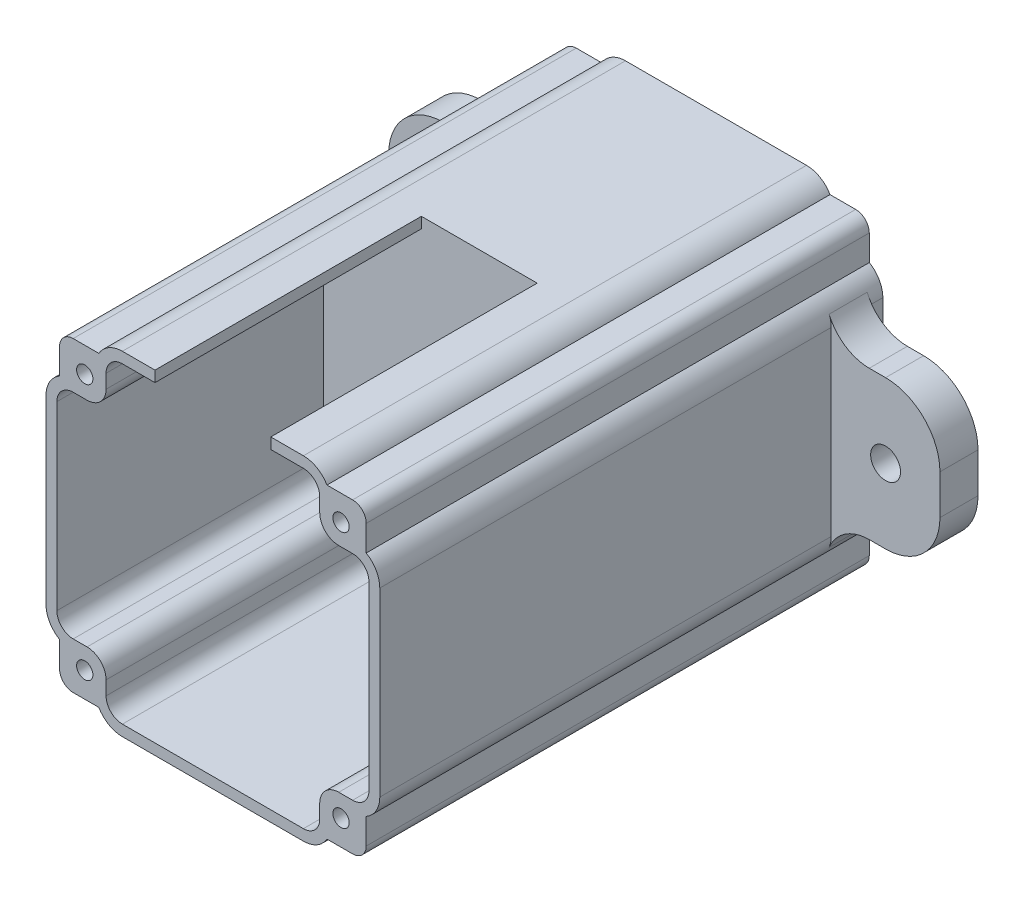
SolidWorks part; units mm, degrees
ref_plane "Front Plane" through (0, 0, 0) normal (0, 0, 1) x (1, 0, 0)
ref_plane "Top Plane" through (0, 0, 0) normal (0, 1, 0) x (1, 0, 0)
ref_plane "Right Plane" through (0, 0, 0) normal (1, 0, 0) x (0, 0, -1)
sketch "Sketch1" plane through (0, 0, -54) normal (0, 0, -1) x (-1, 0, 0)
  line L0 (-25.7, -19.65) -> (-23.15, -19.65)
  line L1 (-19.65, -23.15) -> (-19.65, -25.7)
  line L2 (-16.65, -28.7) -> (16.65, -28.7)
  line L3 (19.65, -25.7) -> (19.65, -23.15)
  line L4 (23.15, -19.65) -> (25.7, -19.65)
  line L5 (28.7, -16.65) -> (28.7, 16.65)
  line L6 (25.7, 19.65) -> (23.15, 19.65)
  line L7 (19.65, 23.15) -> (19.65, 25.7)
  line L8 (16.65, 28.7) -> (10.65, 28.7)
  line L9 (-19.65, 25.7) -> (-19.65, 23.15)
  line L10 (-23.15, 19.65) -> (-25.7, 19.65)
  line L11 (-28.7, 16.65) -> (-28.7, -16.65)
  line L12 (-25.7, -18.65) -> (-23.15, -18.65)
  line L13 (-18.65, -23.15) -> (-18.65, -25.7)
  line L14 (-16.65, -27.7) -> (16.65, -27.7)
  line L15 (18.65, -25.7) -> (18.65, -23.15)
  line L16 (23.15, -18.65) -> (25.7, -18.65)
  line L17 (27.7, -16.65) -> (27.7, 16.65)
  line L18 (25.7, 18.65) -> (23.15, 18.65)
  line L19 (18.65, 23.15) -> (18.65, 25.7)
  line L20 (16.65, 27.7) -> (-16.65, 27.7)
  line L21 (-18.65, 25.7) -> (-18.65, 23.15)
  line L22 (-23.15, 18.65) -> (-25.7, 18.65)
  line L23 (-27.7, 16.65) -> (-27.7, -16.65)
  line L24 (-25.7, -18.65) -> (-23.15, -18.65) construction
  line L25 (-18.65, -23.15) -> (-18.65, -25.7) construction
  line L26 (-16.65, -27.7) -> (16.65, -27.7) construction
  line L27 (18.65, -25.7) -> (18.65, -23.15) construction
  line L28 (23.15, -18.65) -> (25.7, -18.65) construction
  line L29 (27.7, -16.65) -> (27.7, 16.65) construction
  line L30 (25.7, 18.65) -> (23.15, 18.65) construction
  line L31 (18.65, 23.15) -> (18.65, 25.7) construction
  line L32 (16.65, 27.7) -> (-16.65, 27.7) construction
  line L33 (-18.65, 25.7) -> (-18.65, 23.15) construction
  line L34 (-23.15, 18.65) -> (-25.7, 18.65) construction
  line L35 (-27.7, 16.65) -> (-27.7, -16.65) construction
  line L36 (-25.7, -21.65) -> (-23.15, -21.65)
  line L37 (-21.65, -23.15) -> (-21.65, -25.7)
  line L38 (-16.65, -30.7) -> (16.65, -30.7)
  line L39 (21.65, -25.7) -> (21.65, -23.15)
  line L40 (23.15, -21.65) -> (25.7, -21.65)
  line L41 (30.7, -16.65) -> (30.7, 16.65)
  line L42 (25.7, 21.65) -> (23.15, 21.65)
  line L43 (21.65, 23.15) -> (21.65, 25.7)
  line L44 (16.65, 30.7) -> (10.65, 30.7)
  line L45 (-21.65, 25.7) -> (-21.65, 23.15)
  line L46 (-23.15, 21.65) -> (-25.7, 21.65)
  line L47 (-30.7, 16.65) -> (-30.7, -16.65)
  line L48 (-10.65, 30.7) -> (-10.65, 28.7)
  line L49 (10.65, 30.7) -> (10.65, 28.7)
  line L50 (-10.65, 30.7) -> (-16.65, 30.7)
  line L51 (16.65, 30.7) -> (-16.65, 30.7) construction
  line L52 (-10.65, 28.7) -> (-16.65, 28.7)
  line L53 (16.65, 28.7) -> (-16.65, 28.7) construction
  arc A0 (-19.65, -23.15) -> (-23.15, -19.65) centre (-23.15, -23.15) ccw
  arc A1 (-19.65, -25.7) -> (-16.65, -28.7) centre (-16.65, -25.7) ccw
  arc A2 (16.65, -28.7) -> (19.65, -25.7) centre (16.65, -25.7) ccw
  arc A3 (23.15, -19.65) -> (19.65, -23.15) centre (23.15, -23.15) ccw
  arc A4 (25.7, -19.65) -> (28.7, -16.65) centre (25.7, -16.65) ccw
  arc A5 (28.7, 16.65) -> (25.7, 19.65) centre (25.7, 16.65) ccw
  arc A6 (19.65, 23.15) -> (23.15, 19.65) centre (23.15, 23.15) ccw
  arc A7 (19.65, 25.7) -> (16.65, 28.7) centre (16.65, 25.7) ccw
  arc A8 (-16.65, 28.7) -> (-19.65, 25.7) centre (-16.65, 25.7) ccw
  arc A9 (-23.15, 19.65) -> (-19.65, 23.15) centre (-23.15, 23.15) ccw
  arc A10 (-25.7, 19.65) -> (-28.7, 16.65) centre (-25.7, 16.65) ccw
  arc A11 (-28.7, -16.65) -> (-25.7, -19.65) centre (-25.7, -16.65) ccw
  arc A12 (-27.7, -16.65) -> (-25.7, -18.65) centre (-25.7, -16.65) ccw
  arc A13 (-18.65, -23.15) -> (-23.15, -18.65) centre (-23.15, -23.15) ccw
  arc A14 (-18.65, -25.7) -> (-16.65, -27.7) centre (-16.65, -25.7) ccw
  arc A15 (16.65, -27.7) -> (18.65, -25.7) centre (16.65, -25.7) ccw
  arc A16 (23.15, -18.65) -> (18.65, -23.15) centre (23.15, -23.15) ccw
  arc A17 (25.7, -18.65) -> (27.7, -16.65) centre (25.7, -16.65) ccw
  arc A18 (27.7, 16.65) -> (25.7, 18.65) centre (25.7, 16.65) ccw
  arc A19 (18.65, 23.15) -> (23.15, 18.65) centre (23.15, 23.15) ccw
  arc A20 (18.65, 25.7) -> (16.65, 27.7) centre (16.65, 25.7) ccw
  arc A21 (-16.65, 27.7) -> (-18.65, 25.7) centre (-16.65, 25.7) ccw
  arc A22 (-23.15, 18.65) -> (-18.65, 23.15) centre (-23.15, 23.15) ccw
  arc A23 (-25.7, 18.65) -> (-27.7, 16.65) centre (-25.7, 16.65) ccw
  arc A24 (-27.7, -16.65) -> (-25.7, -18.65) centre (-25.7, -16.65) ccw construction
  arc A25 (-18.65, -23.15) -> (-23.15, -18.65) centre (-23.15, -23.15) ccw construction
  arc A26 (-18.65, -25.7) -> (-16.65, -27.7) centre (-16.65, -25.7) ccw construction
  arc A27 (16.65, -27.7) -> (18.65, -25.7) centre (16.65, -25.7) ccw construction
  arc A28 (23.15, -18.65) -> (18.65, -23.15) centre (23.15, -23.15) ccw construction
  arc A29 (25.7, -18.65) -> (27.7, -16.65) centre (25.7, -16.65) ccw construction
  arc A30 (27.7, 16.65) -> (25.7, 18.65) centre (25.7, 16.65) ccw construction
  arc A31 (18.65, 23.15) -> (23.15, 18.65) centre (23.15, 23.15) ccw construction
  arc A32 (18.65, 25.7) -> (16.65, 27.7) centre (16.65, 25.7) ccw construction
  arc A33 (-16.65, 27.7) -> (-18.65, 25.7) centre (-16.65, 25.7) ccw construction
  arc A34 (-23.15, 18.65) -> (-18.65, 23.15) centre (-23.15, 23.15) ccw construction
  arc A35 (-25.7, 18.65) -> (-27.7, 16.65) centre (-25.7, 16.65) ccw construction
  arc A36 (-21.65, -23.15) -> (-23.15, -21.65) centre (-23.15, -23.15) ccw
  arc A37 (-21.65, -25.7) -> (-16.65, -30.7) centre (-16.65, -25.7) ccw
  arc A38 (16.65, -30.7) -> (21.65, -25.7) centre (16.65, -25.7) ccw
  arc A39 (23.15, -21.65) -> (21.65, -23.15) centre (23.15, -23.15) ccw
  arc A40 (25.7, -21.65) -> (30.7, -16.65) centre (25.7, -16.65) ccw
  arc A41 (30.7, 16.65) -> (25.7, 21.65) centre (25.7, 16.65) ccw
  arc A42 (21.65, 23.15) -> (23.15, 21.65) centre (23.15, 23.15) ccw
  arc A43 (21.65, 25.7) -> (16.65, 30.7) centre (16.65, 25.7) ccw
  arc A44 (-16.65, 30.7) -> (-21.65, 25.7) centre (-16.65, 25.7) ccw
  arc A45 (-23.15, 21.65) -> (-21.65, 23.15) centre (-23.15, 23.15) ccw
  arc A46 (-25.7, 21.65) -> (-30.7, 16.65) centre (-25.7, 16.65) ccw
  arc A47 (-30.7, -16.65) -> (-25.7, -21.65) centre (-25.7, -16.65) ccw
  dimension "D4" = 6
  dimension "D5" = 6
  dimension "D1" = 0
  dimension "D2" = 1
  dimension "D3" = 2
extrude "Boss-Extrude1" add sketch "Sketch1" against normal up to surface (49 mm away)
sketch "Sketch2" plane through (0, 0, -54) normal (0, 0, -1) x (-1, 0, 0)
  line L0 (-10.65, 30.7) -> (10.65, 30.7)
  line L12 (-25.7, -21.65) -> (-23.15, -21.65)
  line L13 (-21.65, -23.15) -> (-21.65, -25.7)
  line L14 (-16.65, -30.7) -> (16.65, -30.7)
  line L15 (21.65, -25.7) -> (21.65, -23.15)
  line L16 (23.15, -21.65) -> (25.7, -21.65)
  line L17 (30.7, -16.65) -> (30.7, 16.65)
  line L18 (25.7, 21.65) -> (23.15, 21.65)
  line L19 (21.65, 23.15) -> (21.65, 25.7)
  line L20 (16.65, 30.7) -> (10.65, 30.7)
  line L21 (-21.65, 25.7) -> (-21.65, 23.15)
  line L22 (-23.15, 21.65) -> (-25.7, 21.65)
  line L23 (-30.7, 16.65) -> (-30.7, -16.65)
  line L24 (-25.7, -21.65) -> (-23.15, -21.65)
  line L25 (-21.65, -23.15) -> (-21.65, -25.7)
  line L26 (-16.65, -30.7) -> (16.65, -30.7)
  line L27 (21.65, -25.7) -> (21.65, -23.15)
  line L28 (23.15, -21.65) -> (25.7, -21.65)
  line L29 (30.7, -16.65) -> (30.7, 16.65)
  line L30 (25.7, 21.65) -> (23.15, 21.65)
  line L31 (21.65, 23.15) -> (21.65, 25.7)
  line L32 (16.65, 30.7) -> (10.65, 30.7)
  line L33 (-21.65, 25.7) -> (-21.65, 23.15)
  line L34 (-23.15, 21.65) -> (-25.7, 21.65)
  line L35 (-30.7, 16.65) -> (-30.7, -16.65)
  line L52 (-28.7, -16.65) -> (-28.7, 16.65)
  line L54 (-25.7, 19.65) -> (-23.15, 19.65)
  line L56 (-19.65, 23.15) -> (-19.65, 25.7)
  line L58 (-16.65, 28.7) -> (-10.65, 28.7)
  line L60 (-10.65, 28.7) -> (-10.65, 30.7)
  line L62 (-10.65, 30.7) -> (-16.65, 30.7)
  line L63 (-10.65, 30.7) -> (-16.65, 30.7)
  line L64 (10.65, 30.7) -> (10.65, 28.7)
  line L66 (10.65, 28.7) -> (16.65, 28.7)
  line L68 (19.65, 25.7) -> (19.65, 23.15)
  line L70 (23.15, 19.65) -> (25.7, 19.65)
  line L72 (28.7, 16.65) -> (28.7, -16.65)
  line L74 (25.7, -19.65) -> (23.15, -19.65)
  line L76 (19.65, -23.15) -> (19.65, -25.7)
  line L78 (16.65, -28.7) -> (-16.65, -28.7)
  line L80 (-19.65, -25.7) -> (-19.65, -23.15)
  line L82 (-23.15, -19.65) -> (-25.7, -19.65)
  arc A12 (-30.7, -16.65) -> (-25.7, -21.65) centre (-25.7, -16.65) ccw
  arc A13 (-21.65, -23.15) -> (-23.15, -21.65) centre (-23.15, -23.15) ccw
  arc A14 (-21.65, -25.7) -> (-16.65, -30.7) centre (-16.65, -25.7) ccw
  arc A15 (16.65, -30.7) -> (21.65, -25.7) centre (16.65, -25.7) ccw
  arc A16 (23.15, -21.65) -> (21.65, -23.15) centre (23.15, -23.15) ccw
  arc A17 (25.7, -21.65) -> (30.7, -16.65) centre (25.7, -16.65) ccw
  arc A18 (30.7, 16.65) -> (25.7, 21.65) centre (25.7, 16.65) ccw
  arc A19 (21.65, 23.15) -> (23.15, 21.65) centre (23.15, 23.15) ccw
  arc A20 (21.65, 25.7) -> (16.65, 30.7) centre (16.65, 25.7) ccw
  arc A21 (-16.65, 30.7) -> (-21.65, 25.7) centre (-16.65, 25.7) ccw
  arc A22 (-23.15, 21.65) -> (-21.65, 23.15) centre (-23.15, 23.15) ccw
  arc A23 (-25.7, 21.65) -> (-30.7, 16.65) centre (-25.7, 16.65) ccw
  arc A24 (-30.7, -16.65) -> (-25.7, -21.65) centre (-25.7, -16.65) ccw
  arc A25 (-21.65, -23.15) -> (-23.15, -21.65) centre (-23.15, -23.15) ccw
  arc A26 (-21.65, -25.7) -> (-16.65, -30.7) centre (-16.65, -25.7) ccw
  arc A27 (16.65, -30.7) -> (21.65, -25.7) centre (16.65, -25.7) ccw
  arc A28 (23.15, -21.65) -> (21.65, -23.15) centre (23.15, -23.15) ccw
  arc A29 (25.7, -21.65) -> (30.7, -16.65) centre (25.7, -16.65) ccw
  arc A30 (30.7, 16.65) -> (25.7, 21.65) centre (25.7, 16.65) ccw
  arc A31 (21.65, 23.15) -> (23.15, 21.65) centre (23.15, 23.15) ccw
  arc A32 (21.65, 25.7) -> (16.65, 30.7) centre (16.65, 25.7) ccw
  arc A33 (-16.65, 30.7) -> (-21.65, 25.7) centre (-16.65, 25.7) ccw
  arc A34 (-23.15, 21.65) -> (-21.65, 23.15) centre (-23.15, 23.15) ccw
  arc A35 (-25.7, 21.65) -> (-30.7, 16.65) centre (-25.7, 16.65) ccw
  arc A48 (-28.7, -16.65) -> (-25.7, -19.65) centre (-25.7, -16.65) ccw
  arc A50 (-25.7, 19.65) -> (-28.7, 16.65) centre (-25.7, 16.65) ccw
  arc A52 (-23.15, 19.65) -> (-19.65, 23.15) centre (-23.15, 23.15) ccw
  arc A54 (-16.65, 28.7) -> (-19.65, 25.7) centre (-16.65, 25.7) ccw
  arc A56 (19.65, 25.7) -> (16.65, 28.7) centre (16.65, 25.7) ccw
  arc A58 (19.65, 23.15) -> (23.15, 19.65) centre (23.15, 23.15) ccw
  arc A60 (28.7, 16.65) -> (25.7, 19.65) centre (25.7, 16.65) ccw
  arc A62 (25.7, -19.65) -> (28.7, -16.65) centre (25.7, -16.65) ccw
  arc A64 (23.15, -19.65) -> (19.65, -23.15) centre (23.15, -23.15) ccw
  arc A66 (16.65, -28.7) -> (19.65, -25.7) centre (16.65, -25.7) ccw
  arc A68 (-19.65, -25.7) -> (-16.65, -28.7) centre (-16.65, -25.7) ccw
  arc A70 (-19.65, -23.15) -> (-23.15, -19.65) centre (-23.15, -23.15) ccw
  dimension "D1" = 0
extrude "Boss-Extrude2" add sketch "Sketch2" along normal blind 1.5
sketch "Sketch3" plane through (0, 0, -55.5) normal (0, 0, -1) x (-1, 0, 0)
  line L5 (-21.65, 25.7) -> (-21.65, 23.15) construction
  line L6 (-23.15, 21.65) -> (-25.7, 21.65) construction
  line L7 (-28.2, 16.65) -> (-28.2, 25.7) construction
  line L13 (-25.7, 28.2) -> (-16.65, 28.2) construction
  line L14 (-21.65, 25.7) -> (-21.65, 23.15)
  line L15 (-23.15, 21.65) -> (-25.7, 21.65)
  line L21 (-28.2, 20.9801) -> (-28.2, 25.7)
  line L22 (-25.7, 28.2) -> (-20.9801, 28.2)
  line L23 (21.65, 23.15) -> (21.65, 25.7) construction
  line L92 (25.7, 21.65) -> (23.15, 21.65) construction
  line L93 (28.2, 25.7) -> (28.2, 16.65) construction
  line L94 (16.65, 28.2) -> (25.7, 28.2) construction
  line L95 (21.65, 23.15) -> (21.65, 25.7)
  line L96 (25.7, 21.65) -> (23.15, 21.65)
  line L97 (28.2, 25.7) -> (28.2, 20.9801)
  line L98 (20.9801, 28.2) -> (25.7, 28.2)
  line L99 (-25.7, -21.65) -> (-23.15, -21.65) construction
  line L100 (-21.65, -23.15) -> (-21.65, -25.7) construction
  line L101 (-16.65, -28.2) -> (-25.7, -28.2) construction
  line L102 (-28.2, -25.7) -> (-28.2, -16.65) construction
  line L103 (-25.7, -21.65) -> (-23.15, -21.65)
  line L104 (-21.65, -23.15) -> (-21.65, -25.7)
  line L105 (-20.9801, -28.2) -> (-25.7, -28.2)
  line L106 (-28.2, -25.7) -> (-28.2, -20.9801)
  line L107 (25.7, -28.2) -> (16.65, -28.2) construction
  line L108 (21.65, -25.7) -> (21.65, -23.15) construction
  line L109 (23.15, -21.65) -> (25.7, -21.65) construction
  line L110 (25.7, -28.2) -> (20.9801, -28.2)
  line L111 (21.65, -25.7) -> (21.65, -23.15)
  line L112 (23.15, -21.65) -> (25.7, -21.65)
  line L113 (28.2, -16.65) -> (28.2, -25.7) construction
  line L114 (28.2, -20.9801) -> (28.2, -25.7)
  arc A92 (-16.65, 30.7) -> (-21.65, 25.7) centre (-16.65, 25.7) ccw construction
  arc A93 (-23.15, 21.65) -> (-21.65, 23.15) centre (-23.15, 23.15) ccw construction
  arc A94 (-25.7, 21.65) -> (-30.7, 16.65) centre (-25.7, 16.65) ccw construction
  arc A95 (-25.7, 28.2) -> (-28.2, 25.7) centre (-25.7, 25.7) ccw construction
  arc A96 (-20.9801, 28.2) -> (-21.65, 25.7) centre (-16.65, 25.7) ccw
  arc A97 (-23.15, 21.65) -> (-21.65, 23.15) centre (-23.15, 23.15) ccw
  arc A98 (-25.7, 21.65) -> (-28.2, 20.9801) centre (-25.7, 16.65) ccw
  arc A99 (-25.7, 28.2) -> (-28.2, 25.7) centre (-25.7, 25.7) ccw
  arc A100 (21.65, 25.7) -> (16.65, 30.7) centre (16.65, 25.7) ccw construction
  arc A101 (21.65, 23.15) -> (23.15, 21.65) centre (23.15, 23.15) ccw construction
  arc A102 (30.7, 16.65) -> (25.7, 21.65) centre (25.7, 16.65) ccw construction
  arc A103 (28.2, 25.7) -> (25.7, 28.2) centre (25.7, 25.7) ccw construction
  arc A104 (21.65, 25.7) -> (20.9801, 28.2) centre (16.65, 25.7) ccw
  arc A105 (21.65, 23.15) -> (23.15, 21.65) centre (23.15, 23.15) ccw
  arc A106 (28.2, 20.9801) -> (25.7, 21.65) centre (25.7, 16.65) ccw
  arc A107 (28.2, 25.7) -> (25.7, 28.2) centre (25.7, 25.7) ccw
  arc A108 (-30.7, -16.65) -> (-25.7, -21.65) centre (-25.7, -16.65) ccw construction
  arc A109 (-21.65, -23.15) -> (-23.15, -21.65) centre (-23.15, -23.15) ccw construction
  arc A110 (-21.65, -25.7) -> (-16.65, -30.7) centre (-16.65, -25.7) ccw construction
  arc A111 (-28.2, -25.7) -> (-25.7, -28.2) centre (-25.7, -25.7) ccw construction
  arc A112 (-28.2, -20.9801) -> (-25.7, -21.65) centre (-25.7, -16.65) ccw
  arc A113 (-21.65, -23.15) -> (-23.15, -21.65) centre (-23.15, -23.15) ccw
  arc A114 (-21.65, -25.7) -> (-20.9801, -28.2) centre (-16.65, -25.7) ccw
  arc A115 (-28.2, -25.7) -> (-25.7, -28.2) centre (-25.7, -25.7) ccw
  arc A116 (25.7, -28.2) -> (28.2, -25.7) centre (25.7, -25.7) ccw construction
  arc A117 (16.65, -30.7) -> (21.65, -25.7) centre (16.65, -25.7) ccw construction
  arc A118 (23.15, -21.65) -> (21.65, -23.15) centre (23.15, -23.15) ccw construction
  arc A119 (25.7, -21.65) -> (30.7, -16.65) centre (25.7, -16.65) ccw construction
  arc A120 (25.7, -28.2) -> (28.2, -25.7) centre (25.7, -25.7) ccw
  arc A121 (20.9801, -28.2) -> (21.65, -25.7) centre (16.65, -25.7) ccw
  arc A122 (23.15, -21.65) -> (21.65, -23.15) centre (23.15, -23.15) ccw
  arc A123 (25.7, -21.65) -> (28.2, -20.9801) centre (25.7, -16.65) ccw
  arc M25 (-30.7, -16.65) -> (-25.7, -21.65) centre (-25.7, -16.65) ccw
  line M26 (-25.7, -21.65) -> (-23.15, -21.65)
  arc M27 (-23.15, -21.65) -> (-21.65, -23.15) centre (-23.15, -23.15) cw
  line M28 (-21.65, -23.15) -> (-21.65, -25.7)
  arc M29 (-21.65, -25.7) -> (-16.65, -30.7) centre (-16.65, -25.7) ccw
  arc M31 (16.65, -30.7) -> (21.65, -25.7) centre (16.65, -25.7) ccw
  line M32 (21.65, -25.7) -> (21.65, -23.15)
  arc M33 (21.65, -23.15) -> (23.15, -21.65) centre (23.15, -23.15) cw
  line M34 (23.15, -21.65) -> (25.7, -21.65)
  arc M35 (25.7, -21.65) -> (30.7, -16.65) centre (25.7, -16.65) ccw
  arc M37 (30.7, 16.65) -> (25.7, 21.65) centre (25.7, 16.65) ccw
  line M38 (25.7, 21.65) -> (23.15, 21.65)
  arc M39 (23.15, 21.65) -> (21.65, 23.15) centre (23.15, 23.15) cw
  line M40 (21.65, 23.15) -> (21.65, 25.7)
  arc M41 (21.65, 25.7) -> (16.65, 30.7) centre (16.65, 25.7) ccw
  arc M43 (-16.65, 30.7) -> (-21.65, 25.7) centre (-16.65, 25.7) ccw
  line M44 (-21.65, 25.7) -> (-21.65, 23.15)
  arc M45 (-21.65, 23.15) -> (-23.15, 21.65) centre (-23.15, 23.15) cw
  line M46 (-23.15, 21.65) -> (-25.7, 21.65)
  arc M47 (-25.7, 21.65) -> (-30.7, 16.65) centre (-25.7, 16.65) ccw
extrude "Boss-Extrude3" add sketch "Sketch3" against normal up to surface (50.5 mm away) contours M47 M46 M45 M44 M43 | M41 M40 M39 M38 M37 | M29 M28 M27 M26 M25 | M35 M34 M33 M32 M31 region at (24.8618, 24.8618, -55.5) region at (-24.8618, 24.8618, -55.5) region at (24.8618, -24.8618, -55.5) region at (-24.8618, -24.8618, -55.5)
sketch "Sketch4" plane through (0, 0, -5) normal (0, 0, 1) x (1, 0, 0)
  circle A0 centre (-23.57, 23.57) radius 1.5
  circle A1 centre (23.57, 23.57) radius 1.5
  circle A2 centre (-23.57, -23.57) radius 1.5
  circle A3 centre (23.57, -23.57) radius 1.5
  dimension "D1" = 3
extrude "Cut-Extrude1" cut sketch "Sketch4" against normal blind 10
sketch "Sketch5" plane through (0, 0, -55.5) normal (0, 0, -1) x (-1, 0, 0)
  line L12 (28.2, -25.7) -> (28.2, -20.9801)
  line L13 (30.7, -16.65) -> (30.7, 16.65)
  line L14 (28.2, 20.9801) -> (28.2, 25.7)
  line L15 (25.7, 28.2) -> (20.9801, 28.2)
  line L16 (16.65, 30.7) -> (-16.65, 30.7)
  line L17 (-20.9801, 28.2) -> (-25.7, 28.2)
  line L18 (-28.2, 25.7) -> (-28.2, 20.9801)
  line L19 (-30.7, 16.65) -> (-30.7, -16.65)
  line L20 (-28.2, -20.9801) -> (-28.2, -25.7)
  line L21 (-25.7, -28.2) -> (-20.9801, -28.2)
  line L22 (-16.65, -30.7) -> (16.65, -30.7)
  line L23 (20.9801, -28.2) -> (25.7, -28.2)
  line L24 (28.2, -25.7) -> (28.2, -20.9801)
  line L25 (30.7, -16.65) -> (30.7, 16.65)
  line L26 (28.2, 20.9801) -> (28.2, 25.7)
  line L27 (25.7, 28.2) -> (20.9801, 28.2)
  line L28 (16.65, 30.7) -> (-16.65, 30.7)
  line L29 (-20.9801, 28.2) -> (-25.7, 28.2)
  line L30 (-28.2, 25.7) -> (-28.2, 20.9801)
  line L31 (-30.7, 16.65) -> (-30.7, -16.65)
  line L32 (-28.2, -20.9801) -> (-28.2, -25.7)
  line L33 (-25.7, -28.2) -> (-20.9801, -28.2)
  line L34 (-16.65, -30.7) -> (16.65, -30.7)
  line L35 (20.9801, -28.2) -> (25.7, -28.2)
  arc A12 (28.2, -20.9801) -> (30.7, -16.65) centre (25.7, -16.65) ccw
  arc A13 (30.7, 16.65) -> (28.2, 20.9801) centre (25.7, 16.65) ccw
  arc A14 (28.2, 25.7) -> (25.7, 28.2) centre (25.7, 25.7) ccw
  arc A15 (20.9801, 28.2) -> (16.65, 30.7) centre (16.65, 25.7) ccw
  arc A16 (-16.65, 30.7) -> (-20.9801, 28.2) centre (-16.65, 25.7) ccw
  arc A17 (-25.7, 28.2) -> (-28.2, 25.7) centre (-25.7, 25.7) ccw
  arc A18 (-28.2, 20.9801) -> (-30.7, 16.65) centre (-25.7, 16.65) ccw
  arc A19 (-30.7, -16.65) -> (-28.2, -20.9801) centre (-25.7, -16.65) ccw
  arc A20 (-28.2, -25.7) -> (-25.7, -28.2) centre (-25.7, -25.7) ccw
  arc A21 (-20.9801, -28.2) -> (-16.65, -30.7) centre (-16.65, -25.7) ccw
  arc A22 (16.65, -30.7) -> (20.9801, -28.2) centre (16.65, -25.7) ccw
  arc A23 (25.7, -28.2) -> (28.2, -25.7) centre (25.7, -25.7) ccw
  arc A24 (28.2, -20.9801) -> (30.7, -16.65) centre (25.7, -16.65) ccw
  arc A25 (30.7, 16.65) -> (28.2, 20.9801) centre (25.7, 16.65) ccw
  arc A26 (28.2, 25.7) -> (25.7, 28.2) centre (25.7, 25.7) ccw
  arc A27 (20.9801, 28.2) -> (16.65, 30.7) centre (16.65, 25.7) ccw
  arc A28 (-16.65, 30.7) -> (-20.9801, 28.2) centre (-16.65, 25.7) ccw
  arc A29 (-25.7, 28.2) -> (-28.2, 25.7) centre (-25.7, 25.7) ccw
  arc A30 (-28.2, 20.9801) -> (-30.7, 16.65) centre (-25.7, 16.65) ccw
  arc A31 (-30.7, -16.65) -> (-28.2, -20.9801) centre (-25.7, -16.65) ccw
  arc A32 (-28.2, -25.7) -> (-25.7, -28.2) centre (-25.7, -25.7) ccw
  arc A33 (-20.9801, -28.2) -> (-16.65, -30.7) centre (-16.65, -25.7) ccw
  arc A34 (16.65, -30.7) -> (20.9801, -28.2) centre (16.65, -25.7) ccw
  arc A35 (25.7, -28.2) -> (28.2, -25.7) centre (25.7, -25.7) ccw
  dimension "D1" = 0
extrude "Boss-Extrude4" add sketch "Sketch5" along normal up to surface (42.04 mm away)
sketch "Sketch7" plane through (30.7, 0, 0) normal (1, 0, 0) x (0, 0, -1)
  line L1 (95.04, 13.65) -> (88.04, 13.65)
  line L2 (95.04, 13.65) -> (95.04, -13.65)
  line L3 (95.04, -13.65) -> (88.04, -13.65)
  line L4 (88.04, 13.65) -> (88.04, -13.65)
  line L5 (5, 16.65) -> (97.54, 16.65) construction
  line L6 (5, -16.65) -> (97.54, -16.65) construction
  line L8 (97.54, -16.65) -> (97.54, 16.65) construction
  point P7 (0, 0)
  point P8 (0, 0)
  point P9 (0, 0)
  point P10 (0, 0)
  point P11 (0, 0)
  point P12 (0, 0)
  point P15 (97.54, 13.65)
  point P16 (93.4933, 13.65)
  point P18 (0, 0)
  dimension "D1" = 7
  dimension "D2" = 3
  dimension "D3" = 3
  dimension "D4" = 2.5
extrude "Boss-Extrude5" add sketch "Sketch7" along normal blind 20
fillet "Fillet1" radius 10 2 edges at (50.7, -13.65, -91.54) (50.7, 13.65, -91.54)
fillet "Fillet2" radius 8 2 edges at (30.7, -13.65, -91.54) (30.7, 13.65, -91.54)
mirror "Mirror1" about plane through (0, 0, 0) normal (1, 0, 0) of "Boss-Extrude5"
fillet "Fillet3" radius 10 2 edges at (-50.7, 13.65, -91.54) (-50.7, -13.65, -91.54)
fillet "Fillet4" radius 8 2 edges at (-30.7, -13.65, -91.54) (-30.7, 13.65, -91.54)
sketch "Sketch8" plane through (0, 0, -88.04) normal (0, 0, 1) x (1, 0, 0)
  line L0 (-40.7, 0) -> (40.7, 0) construction
  line L1 (50.7, 3.65) -> (50.7, -3.65) construction
  circle A0 centre (40.7, 0) radius 2.75
  circle A1 centre (-40.7, 0) radius 2.75
  point P4 (0, 0)
  dimension "D1" = 5.5
  dimension "D2" = 10
extrude "Cut-Extrude2" cut sketch "Sketch8" against normal up to surface (9.5 mm away) up to face at (0, 0, -97.54)
